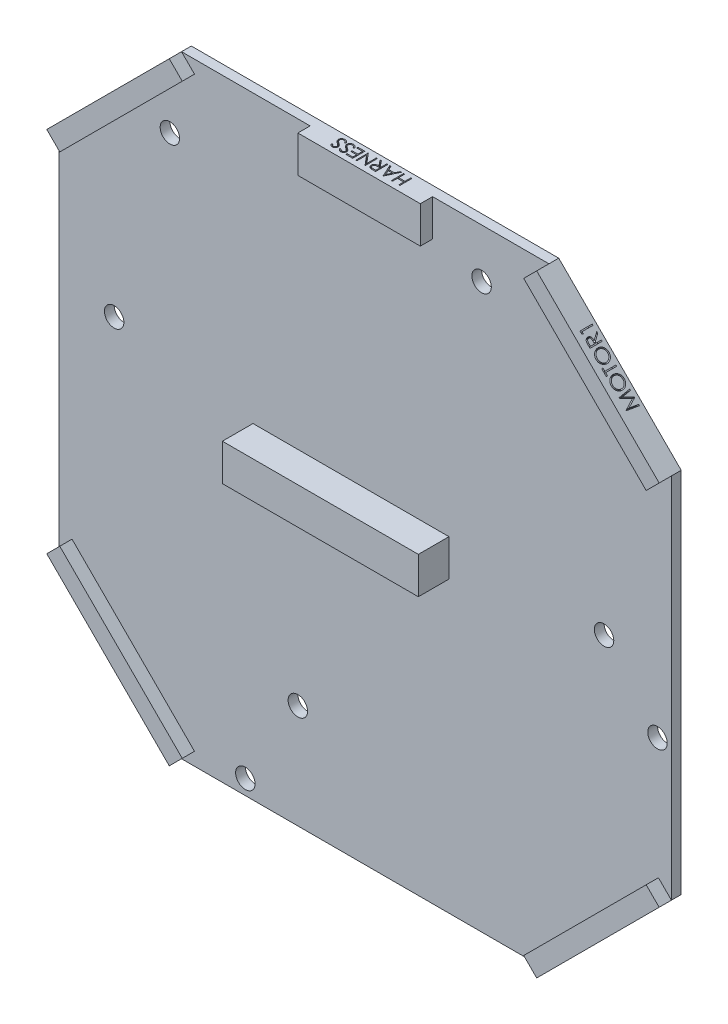
SolidWorks part; units mm, degrees
ref_plane "Front Plane" through (0, 0, 0) normal (0, 0, 1) x (1, 0, 0)
ref_plane "Top Plane" through (0, 0, 0) normal (0, 1, 0) x (1, 0, 0)
ref_plane "Right Plane" through (0, 0, 0) normal (1, 0, 0) x (0, 0, -1)
sketch "Sketch1" plane through (0, 0, 0) normal (0, 0, 1) x (1, 0, 0)
  line L1 (-34.7243, 77.3309) -> (65.2757, 77.3309)
  line L2 (-34.7243, 77.3309) -> (-34.7243, -22.6691)
  line L3 (-34.7243, -22.6691) -> (65.2757, -22.6691)
  line L4 (65.2757, 77.3309) -> (65.2757, -22.6691)
  dimension "D1" = 100
  dimension "D2" = 100
extrude "Boss-Extrude1" add sketch "Sketch1" along normal blind 1.6
sketch "Sketch2" plane through (0, 0, 1.6) normal (0, 0, 1) x (1, 0, 0)
  line L0 (-34.7243, 57.3309) -> (-14.7243, 77.3309)
  line L1 (-34.7243, 77.3309) -> (-34.7243, -22.6691) construction
  line L2 (65.2757, 77.3309) -> (-34.7243, 77.3309) construction
  line L3 (-14.7243, 77.3309) -> (-34.7243, 77.3309)
  line L4 (-34.7243, 77.3309) -> (-34.7243, 57.3309)
  line L5 (-34.7243, -2.6691) -> (-14.7243, -22.6691)
  line L6 (-34.7243, -22.6691) -> (65.2757, -22.6691) construction
  line L7 (-14.7243, -22.6691) -> (-34.7243, -22.6691)
  line L8 (-34.7243, -22.6691) -> (-34.7243, -2.6691)
  line L9 (45.2757, 77.3309) -> (65.2757, 57.3309)
  line L10 (65.2757, -22.6691) -> (65.2757, 77.3309) construction
  line L11 (65.2757, 57.3309) -> (65.2757, 77.3309)
  line L12 (65.2757, 77.3309) -> (45.2757, 77.3309)
  line L13 (65.2757, -2.6691) -> (45.2757, -22.6691)
  line L14 (45.2757, -22.6691) -> (65.2757, -22.6691)
  line L15 (65.2757, -22.6691) -> (65.2757, -2.6691)
  dimension "D1" = 20
  dimension "D2" = 20
  dimension "D3" = 20
  dimension "D4" = 20
  dimension "D5" = 20
  dimension "D6" = 20
  dimension "D7" = 20
  dimension "D8" = 20
extrude "Cut-Extrude1" cut sketch "Sketch2" against normal blind 1.6
sketch "Sketch7" plane through (0, 0, 1.6) normal (0, 0, 1) x (1, 0, 0)
  line L0 (45.2757, 77.3309) -> (-14.7243, 77.3309) construction
  line L1 (-34.7243, 57.3309) -> (-34.7243, -2.6691) construction
  line L2 (65.2757, -2.6691) -> (65.2757, 57.3309) construction
  line L3 (-14.7243, -22.6691) -> (45.2757, -22.6691) construction
  circle A0 centre (-25.7243, 34.3309) radius 1.5875
  circle A1 centre (-16.6243, 64.9049) radius 1.5875
  circle A2 centre (34.2757, 69.3309) radius 1.5875
  circle A3 centre (54.2757, 29.3309) radius 1.5875
  circle A4 centre (62.9997, 19.1809) radius 1.5875
  circle A5 centre (-4.3003, -20.2191) radius 1.5875
  circle A6 centre (4.2757, -5.6691) radius 1.5875
  dimension "D1" = 3.175
  dimension "D16" = 3.175
  dimension "D17" = 3.175
  dimension "D18" = 3.175
  dimension "D19" = 3.175
  dimension "D20" = 3.175
  dimension "D21" = 3.175
  dimension "D2" = 43
  dimension "D3" = 9
  dimension "D4" = 12.426
  dimension "D5" = 18.1
  dimension "D6" = 8
  dimension "D7" = 31
  dimension "D8" = 11
  dimension "D9" = 48
  dimension "D10" = 58.15
  dimension "D11" = 97.724
  dimension "D12" = 39
  dimension "D13" = 17
  dimension "D14" = 30.424
  dimension "D15" = 97.55
extrude "Cut-Extrude2" cut sketch "Sketch7" against normal blind 1.6
sketch "Sketch8" plane through (0, 0, 1.6) normal (0, 0, 1) x (1, 0, 0)
  line L0 (45.2757, 77.3309) -> (-14.7243, 77.3309) construction
  line L1 (-3.0503, 30.5809) -> (28.9497, 30.5809)
  line L2 (-3.0503, 30.5809) -> (-3.0503, 24.5809)
  line L3 (-3.0503, 24.5809) -> (28.9497, 24.5809)
  line L4 (28.9497, 30.5809) -> (28.9497, 24.5809)
  line L5 (-34.7243, 57.3309) -> (-34.7243, -2.6691) construction
  dimension "D1" = 46.75
  dimension "D2" = 31.674
  dimension "D3" = 32
  dimension "D4" = 6
extrude "Boss-Extrude2" add sketch "Sketch8" along normal blind 5
sketch "Sketch10" plane through (0, 0, 1.6) normal (0, 0, 1) x (1, 0, 0)
  line L0 (-34.7243, 57.3309) -> (-14.7243, 77.3309)
  line L1 (-34.7243, 57.3309) -> (-32.603, 55.2096)
  line L2 (-14.7243, 77.3309) -> (-12.603, 75.2096)
  line L3 (-32.603, 55.2096) -> (-12.603, 75.2096)
  line L4 (-34.7243, 57.3309) -> (-14.7243, 77.3309) construction
  line L5 (45.2757, 77.3309) -> (65.2757, 57.3309)
  line L6 (45.2757, 77.3309) -> (43.1543, 75.2096)
  line L7 (65.2757, 57.3309) -> (63.1543, 55.2096)
  line L8 (43.1543, 75.2096) -> (63.1543, 55.2096)
  line L9 (45.2757, 77.3309) -> (65.2757, 57.3309) construction
  line L10 (65.2757, -2.6691) -> (45.2757, -22.6691)
  line L11 (65.2757, -2.6691) -> (63.1543, -0.5478)
  line L12 (45.2757, -22.6691) -> (43.1543, -20.5478)
  line L13 (63.1543, -0.5478) -> (43.1543, -20.5478)
  line L14 (65.2757, -2.6691) -> (45.2757, -22.6691) construction
  line L15 (-14.7243, -22.6691) -> (-34.7243, -2.6691)
  line L16 (-14.7243, -22.6691) -> (-12.603, -20.5478)
  line L17 (-34.7243, -2.6691) -> (-32.603, -0.5478)
  line L18 (-12.603, -20.5478) -> (-32.603, -0.5478)
  line L19 (-14.7243, -22.6691) -> (-34.7243, -2.6691) construction
  dimension "D1" = 3
  dimension "D2" = 3
  dimension "D3" = 3
  dimension "D4" = 3
extrude "Boss-Extrude3" add sketch "Sketch10" along normal blind 2
sketch "Sketch12" plane through (0, 0, 1.6) normal (0, 0, 1) x (1, 0, 0)
  line L0 (-34.7243, 57.3309) -> (-34.7243, -2.6691) construction
  line L1 (6.2757, 77.3309) -> (26.2757, 77.3309)
  line L2 (6.2757, 77.3309) -> (6.2757, 71.3309)
  line L3 (6.2757, 71.3309) -> (26.2757, 71.3309)
  line L4 (26.2757, 77.3309) -> (26.2757, 71.3309)
  line L5 (45.2757, 77.3309) -> (-14.7243, 77.3309) construction
  dimension "D1" = 20
  dimension "D2" = 6
  dimension "D3" = 41
extrude "Boss-Extrude5" add sketch "Sketch12" along normal blind 2
sketch "Sketch13" plane through (0, 77.3309, 0) normal (0, 1, 0) x (1, 0, 0)
  line L0 (22.2842, -0.7074) -> (7.9965, -0.7074) construction
  text T0 "HARNESS" font "Century Gothic" height 2
extrude "Cut-Extrude3" cut sketch "Sketch13" against normal blind 1
sketch "Sketch14" plane through (61.3033, 61.3033, 0) normal (0.7071, 0.7071, 0) x (-0.7071, 0.7071, 0)
  line L0 (3.0965, 0.5495) -> (17.2838, 0.5495) construction
  text T0 "MOTOR1" font "Century Gothic" height 2
extrude "Cut-Extrude4" cut sketch "Sketch14" against normal blind 1
sketch "Sketch15" plane through (33.9724, -33.9724, 0) normal (0.7071, -0.7071, 0) x (0, 0, -1)
  line L0 (-0.6902, 24.0579) -> (-0.6902, 38.0824) construction
  text T0 "MOTOR2" font "Century Gothic" height 2
extrude "Cut-Extrude5" cut sketch "Sketch15" against normal blind 1
sketch "Sketch16" plane through (-18.6967, -18.6967, 0) normal (-0.7071, -0.7071, 0) x (0, 0, 1)
  line L0 (0.5835, 14.6636) -> (0.5835, -1.3289) construction
  text T0 "MOTOR3" font "Century Gothic" height 2
extrude "Cut-Extrude6" cut sketch "Sketch16" against normal blind 1
sketch "Sketch17" plane through (-46.0276, 46.0276, 0) normal (-0.7071, 0.7071, 0) x (0, 0, 1)
  line L0 (0.4171, 35.2596) -> (0.4171, 22.3688) construction
  text T0 "MOTOR4" font "Century Gothic" height 2
extrude "Cut-Extrude7" cut sketch "Sketch17" against normal blind 1
